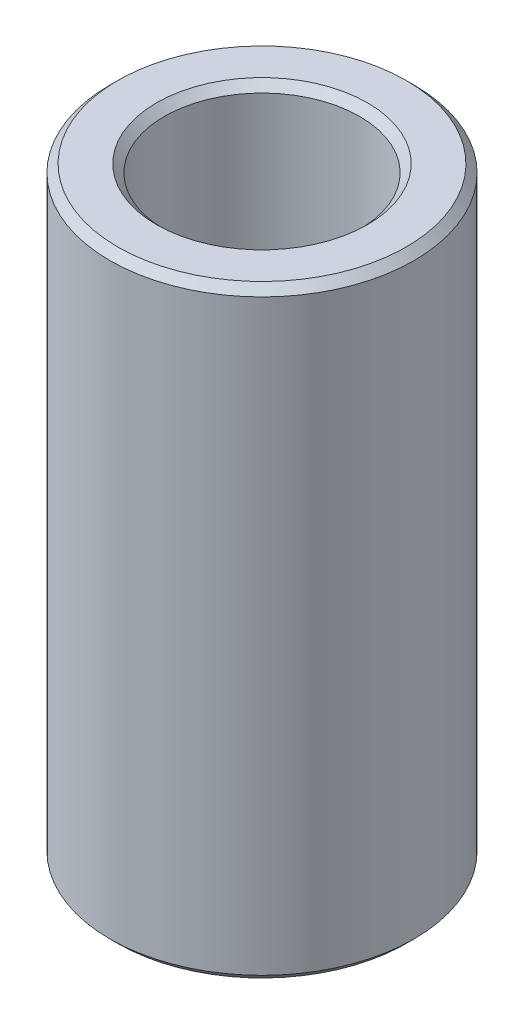
SolidWorks part; units mm, degrees
ref_plane "Front Plane" through (0, 0, 0) normal (0, 0, 1) x (1, 0, 0)
ref_plane "Top Plane" through (0, 0, 0) normal (0, 1, 0) x (1, 0, 0)
ref_plane "Right Plane" through (0, 0, 0) normal (1, 0, 0) x (0, 0, -1)
sketch "Sketch1" plane through (0, 0, 0) normal (0, 1, 0) x (1, 0, 0)
  circle A0 centre (0, 0) radius 50
  dimension "SLEEVE_OD" = 100
extrude "Boss-Extrude1" add sketch "Sketch1" along normal blind 198.3257
sketch "Sketch2" plane through (0, 0, 0) normal (0, 1, 0) x (1, 0, 0)
  circle A0 centre (0, 0) radius 32.1163
  dimension "BORE_D" = 64.2325
extrude "Cut-Extrude1" cut sketch "Sketch2" along normal through all
chamfer "Chamfer1" distance 2.5811 angle 45 4 edges at (0, 198.3257, 32.1163) (0, 0, 32.1163) (0, 0, 50) (0, 198.3257, 50)
